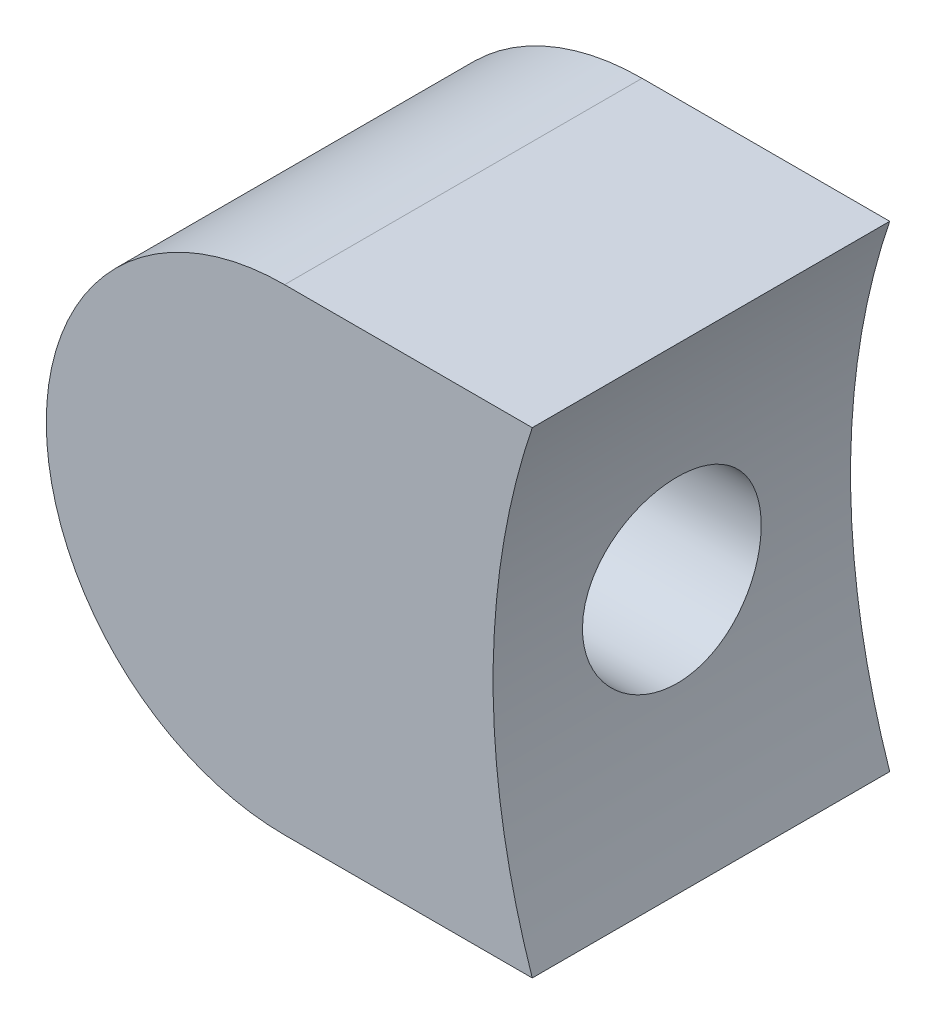
SolidWorks part; units mm, degrees
ref_plane "Ön Düzlem" through (0, 0, 0) normal (0, 0, 1) x (1, 0, 0)
ref_plane "Üst Düzlem" through (0, 0, 0) normal (0, 1, 0) x (1, 0, 0)
ref_plane "Sağ Düzlem" through (0, 0, 0) normal (1, 0, 0) x (0, 0, -1)
sketch "Sketch1" plane through (0, 0, 0) normal (0, 0, 1) x (1, 0, 0)
  line L0 (-11.8427, 4) -> (-20, 4)
  line L1 (-20, 4) -> (-20, -4)
  line L2 (-20, -4) -> (-11.8427, -4)
  arc A0 (-11.8427, 4) -> (-11.8427, -4) centre (0, 0) ccw
  point P8 (-20, 0)
  dimension "D1" = 25
  dimension "D2" = 8
  dimension "D3" = 20
extrude "Boss-Extrude1" add sketch "Sketch1" along normal blind 6
sketch "Sketch2" plane through (-20, 0, 0) normal (-1, 0, 0) x (0, 0, 1)
  line L0 (6, -4) -> (0, -4) construction
  circle A0 centre (3, 0) radius 1.5
  point P8 (3, -4)
  dimension "D1" = 3
extrude "Cut-Extrude1" cut sketch "Sketch2" against normal blind 10
fillet "Fillet1" radius 4 2 edges at (-20, 4, 3) (-20, -4, 3)
